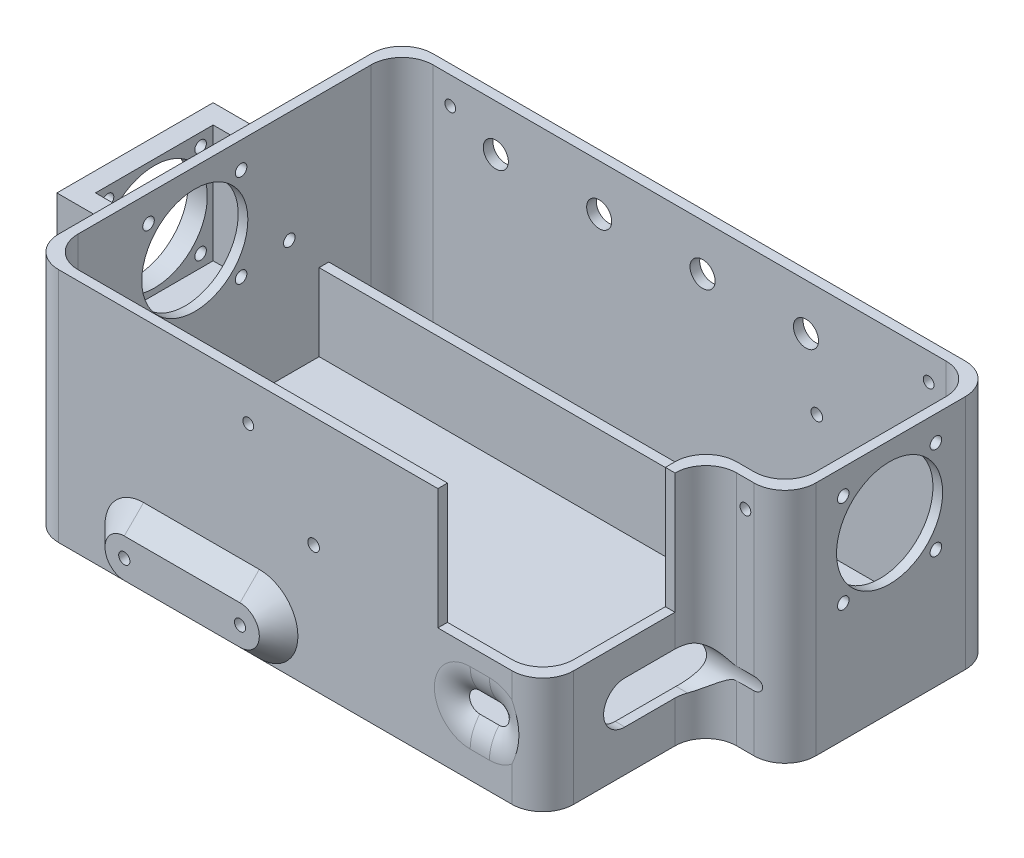
SolidWorks part; units mm, degrees
ref_plane "Front Plane" through (0, 0, 0) normal (0, 0, 1) x (1, 0, 0)
ref_plane "Top Plane" through (0, 0, 0) normal (0, 1, 0) x (1, 0, 0)
ref_plane "Right Plane" through (0, 0, 0) normal (1, 0, 0) x (0, 0, -1)
sketch "Sketch1" plane through (0, 0, 0) normal (0, 1, 0) x (1, 0, 0)
  line L1 (-74.5, 46) -> (74.5, 46)
  line L2 (-74.5, 46) -> (-74.5, -46)
  line L3 (-74.5, -46) -> (74.5, -46)
  line L4 (74.5, 46) -> (74.5, -46)
  line L5 (-74.5, 46) -> (74.5, -46) construction
  line L6 (-74.5, -46) -> (74.5, 46) construction
  point P0 (0, 0)
  dimension "D1" = 149
  dimension "D2" = 92
extrude "Boss-Extrude1" add sketch "Sketch1" along normal blind 2.5
sketch "Sketch2" plane through (0, 2.5, 0) normal (0, 1, 0) x (1, 0, 0)
  line L0 (77, -48.5) -> (77, 48.5)
  line L1 (77, 48.5) -> (-77, 48.5)
  line L2 (-77, 48.5) -> (-77, -48.5)
  line L3 (-77, -48.5) -> (77, -48.5)
  line L4 (74.5, -46) -> (74.5, 46)
  line L5 (74.5, 46) -> (-74.5, 46)
  line L6 (-74.5, 46) -> (-74.5, -46)
  line L7 (-74.5, -46) -> (74.5, -46)
  line L8 (74.5, -46) -> (74.5, 46)
  line L9 (74.5, 46) -> (-74.5, 46)
  line L10 (-74.5, 46) -> (-74.5, -46)
  line L11 (-74.5, -46) -> (74.5, -46)
  dimension "D1" = 0
  dimension "D2" = 2.5
extrude "Boss-Extrude2" add sketch "Sketch2" along normal blind 61.28 from surface at -2.5 starting at face at (0, 0, 0)
sketch "Sketch3" plane through (0, 0, 0) normal (0, 0, 1) x (1, 0, 0)
  line L0 (-77, 49.28) -> (77, 49.28) construction
  line L1 (-77, 61.28) -> (-77, 0) construction
  line L2 (77, 61.28) -> (77, 0) construction
  line L4 (-77, 61.28) -> (77, 61.28) construction
  circle A0 centre (-50.2, 49.28) radius 3.25
  circle A1 centre (-23.4, 49.28) radius 3.25
  circle A2 centre (3.4, 49.28) radius 3.25
  circle A3 centre (30.2, 49.28) radius 3.25
  dimension "D1" = 6.5
  dimension "D2" = 26.8
  dimension "D4" = 12
  dimension "D3" = 4
extrude "Cut-Extrude1" cut sketch "Sketch3" against normal blind 53.78
sketch "Sketch4" plane through (0, 2.5, 0) normal (0, 1, 0) x (1, 0, 0)
  line L0 (-74.5, -33.59) -> (74.5, -33.59) construction
  line L1 (-74.5, 46) -> (-74.5, -46) construction
  line L2 (74.5, -46) -> (74.5, 46) construction
  line L3 (-74.5, 15.41) -> (74.5, 15.41) construction
  line L4 (-74.5, 46) -> (-74.5, -46) construction
  line L5 (74.5, -46) -> (74.5, 46) construction
  line L6 (-74.5, -46) -> (74.5, -46) construction
  line L7 (-74.5, -46) -> (74.5, -46) construction
  line L8 (0, -1.375) -> (0, 1.375) construction
  line L9 (-68.5, 18.41) -> (-74.5, 18.41)
  line L10 (-68.5, 18.41) -> (-68.5, 12.41)
  line L11 (-68.5, 12.41) -> (-74.5, 12.41)
  line L12 (-74.5, 18.41) -> (-74.5, 12.41)
  line L13 (-68.5, 18.41) -> (-74.5, 12.41) construction
  line L14 (-68.5, 12.41) -> (-74.5, 18.41) construction
  line L15 (68.5, 12.41) -> (74.5, 18.41) construction
  line L16 (68.5, 18.41) -> (74.5, 12.41) construction
  line L17 (74.5, 18.41) -> (74.5, 12.41)
  line L18 (68.5, 12.41) -> (74.5, 12.41)
  line L19 (68.5, 18.41) -> (68.5, 12.41)
  line L20 (68.5, 18.41) -> (74.5, 18.41)
  line L21 (-74.5, -9.09) -> (74.5, -9.09) construction
  line L22 (-74.5, -33.59) -> (0, -9.09) construction
  line L23 (0, -9.09) -> (74.5, 15.41) construction
  line L24 (68.5, -36.59) -> (74.5, -30.59) construction
  line L25 (68.5, -30.59) -> (74.5, -36.59) construction
  line L26 (-68.5, -30.59) -> (-74.5, -36.59) construction
  line L27 (-68.5, -36.59) -> (-74.5, -30.59) construction
  line L28 (-74.5, -33.59) -> (74.5, -33.59) construction
  line L29 (68.5, -36.59) -> (74.5, -36.59)
  line L30 (68.5, -36.59) -> (68.5, -30.59)
  line L31 (68.5, -30.59) -> (74.5, -30.59)
  line L32 (74.5, -36.59) -> (74.5, -30.59)
  line L33 (-74.5, -36.59) -> (-74.5, -30.59)
  line L34 (-68.5, -30.59) -> (-74.5, -30.59)
  line L35 (-68.5, -36.59) -> (-68.5, -30.59)
  line L36 (-68.5, -36.59) -> (-74.5, -36.59)
  point P16 (-71.5, 15.41)
  point P27 (71.5, 15.41)
  point P39 (71.5, -33.59)
  point P40 (-71.5, -33.59)
  dimension "D1" = 12.41
  dimension "D2" = 61.41
  dimension "D3" = 6
  dimension "D4" = 6
sketch "Sketch5" plane through (0, 2.5, 0) normal (0, 1, 0) x (1, 0, 0)
  line L0 (-74.5, 46) -> (-74.5, -46) construction
  line L1 (-74.5, 24.5) -> (74.5, 24.5)
  line L2 (-74.5, 24.5) -> (-74.5, 27)
  line L3 (-74.5, 27) -> (74.5, 27)
  line L4 (74.5, 24.5) -> (74.5, 27)
  line L5 (74.5, -46) -> (74.5, 46) construction
  line L6 (-74.5, -46) -> (74.5, -46) construction
  dimension "D1" = 2.5
  dimension "D2" = 70.5
extrude "Boss-Extrude4" add sketch "Sketch5" along normal blind 20
sketch "Sketch6" plane through (-77, 0, 0) normal (-1, 0, 0) x (0, 0, 1)
  line L0 (-18.41, 2.5) -> (-12.41, 2.5) construction
  line L1 (48.5, 61.28) -> (48.5, 0) construction
  circle A0 centre (32.22, 32.5) radius 1.5
  circle A1 centre (-16.78, 32.5) radius 1.5
  dimension "D1" = 3
  dimension "D2" = 30
  dimension "D3" = 16.28
  dimension "D4" = 49
extrude "Cut-Extrude2" cut sketch "Sketch6" against normal up to next
sketch "Sketch8" plane through (0, 2.5, 0) normal (0, 1, 0) x (1, 0, 0)
  line L0 (-74.5, -46) -> (74.5, -46) construction
  line L1 (54, -46) -> (56.5, -46)
  line L2 (54, -46) -> (54, -6.25)
  line L3 (54, -6.25) -> (56.5, -6.25)
  line L4 (56.5, -46) -> (56.5, -6.25)
  line L5 (-74.5, 46) -> (-74.5, -46) construction
  line L6 (74.5, -46) -> (74.5, 46) construction
  line L7 (54, -6.25) -> (74.5, -6.25)
  line L8 (54, -6.25) -> (54, -3.75)
  line L9 (54, -3.75) -> (74.5, -3.75)
  line L10 (74.5, -6.25) -> (74.5, -3.75)
  line M6 (74.5, -46) -> (74.5, 24.5)
  line M9 (-74.5, -46) -> (74.5, -46)
  dimension "D1" = 2.5
  dimension "D2" = 128.5
  dimension "D3" = 39.75
  dimension "D4" = 2.5
extrude "Boss-Extrude5" add sketch "Sketch8" along normal blind 27.5 contours L4 L3 L2 M9 | L9 L8 L3 L7 M6
sketch "Sketch9" plane through (0, 61.28, 0) normal (0, 1, 0) x (1, 0, 0)
  line L1 (77, -48.5) -> (56.5, -48.5)
  line L2 (77, -48.5) -> (77, -6.25)
  line L3 (77, -6.25) -> (56.5, -6.25)
  line L4 (56.5, -48.5) -> (56.5, -6.25)
extrude "Cut-Extrude4" cut sketch "Sketch9" against normal through all
sketch "Sketch10" plane through (0, 61.28, 0) normal (0, 1, 0) x (1, 0, 0)
  line L0 (54, -3.75) -> (74.5, -3.75) construction
  line L1 (56.5, -48.5) -> (29.28, -48.5)
  line L2 (56.5, -48.5) -> (56.5, -3.75)
  line L3 (56.5, -3.75) -> (29.28, -3.75)
  line L4 (29.28, -48.5) -> (29.28, -3.75)
  dimension "D1" = 27.22
extrude "Cut-Extrude5" cut sketch "Sketch10" against normal up to surface (31.28 mm away) up to face at (61.6667, 30, 18.6667)
sketch "Sketch11" plane through (0, 22.5, 0) normal (0, 1, 0) x (1, 0, 0)
  line L0 (-74.5, 24.5) -> (74.5, 24.5) construction
  line L1 (74.5, 27) -> (34.5, 27)
  line L2 (74.5, 27) -> (74.5, 24.5)
  line L3 (74.5, 24.5) -> (34.5, 24.5)
  line L4 (34.5, 27) -> (34.5, 24.5)
  dimension "D1" = 40
extrude "Cut-Extrude6" cut sketch "Sketch11" against normal up to surface (20 mm away) up to face at (0, 2.5, -36.5)
fillet "Fillet1" radius 8 12 edges at (-74.5, 31.89, 46) (-77, 30.64, 48.5) (-74.5, 31.89, -46) (-77, 30.64, -48.5) (74.5, 31.89, -46) (77, 30.64, -48.5) (74.5, 16.25, 3.75) (77, 30.64, 6.25) (54, 16.25, 3.75) (56.5, 15, 6.25) (54, 16.25, 46) (56.5, 15, 48.5)
sketch "Sketch12" plane through (56.5, 0, 0) normal (1, 0, 0) x (0, 0, -1)
  line L0 (-56.3116, 16.25) -> (58.0085, 16.25) construction
  line L1 (24.5, 2.5) -> (-38, 2.5) construction
  line L2 (-27.25, 16.25) -> (-11.5, 16.25) construction
  line L3 (-27.25, 21.75) -> (-11.5, 21.75)
  line L4 (-27.25, 10.75) -> (-11.5, 10.75)
  line L6 (-46, 30) -> (-46, 2.5) construction
  arc A0 (-27.25, 21.75) -> (-27.25, 10.75) centre (-27.25, 16.25) ccw
  arc A1 (-11.5, 10.75) -> (-11.5, 21.75) centre (-11.5, 16.25) ccw
  point P6 (-19.375, 16.25)
  point P11 (-6, 16.25)
  point P16 (-32.75, 16.25)
  dimension "D1" = 13.75
  dimension "D2" = 40
  dimension "D3" = 11
extrude "Cut-Extrude7" cut sketch "Sketch12" against normal up to next and the other way up to next
sketch "Sketch13" plane through (0, 0, 48.5) normal (0, 0, 1) x (1, 0, 0)
  line L0 (-77, 32.5) -> (24.7107, 32.5) construction
  line L1 (-77, 0) -> (-77, 61.28) construction
  line L2 (-77, 34) -> (-77, 31) construction
  circle A0 centre (-2.92, 32.5) radius 1.5
  dimension "D2" = 3
  dimension "D1" = 74.08
extrude "Cut-Extrude8" cut sketch "Sketch13" against normal up to next
sketch "Sketch15" plane through (0, 30, 0) normal (0, 1, 0) x (1, 0, 0)
  line L0 (56.5, -14.25) -> (54, -14.25)
  line L8 (64.5, -6.25) -> (69, -6.25)
  line L9 (74.5, -4.0595) -> (74.5, 4.25)
  line L10 (66.5, -3.75) -> (62, -3.75)
  line L11 (54, -11.75) -> (54, -38)
  line L12 (46, -46) -> (29.28, -46)
  line L13 (29.28, -46) -> (29.28, -48.5)
  line L14 (29.28, -48.5) -> (48.5, -48.5)
  line L15 (56.5, -40.5) -> (56.5, -14.25)
  line L16 (64.5, -6.25) -> (69, -6.25)
  line L17 (74.5, -4.0595) -> (74.5, 4.25)
  line L18 (66.5, -3.75) -> (62, -3.75)
  line L19 (54, -11.75) -> (54, -14.25)
  arc A6 (69, -6.25) -> (74.5, -4.0595) centre (69, 1.75) ccw
  arc A7 (66.5, -3.75) -> (74.5, 4.25) centre (66.5, 4.25) ccw
  arc A8 (62, -3.75) -> (54, -11.75) centre (62, -11.75) ccw
  arc A9 (46, -46) -> (54, -38) centre (46, -38) ccw
  arc A10 (48.5, -48.5) -> (56.5, -40.5) centre (48.5, -40.5) ccw
  arc A11 (64.5, -6.25) -> (56.5, -14.25) centre (64.5, -14.25) ccw
  arc A12 (69, -6.25) -> (74.5, -4.0595) centre (69, 1.75) ccw
  arc A13 (66.5, -3.75) -> (74.5, 4.25) centre (66.5, 4.25) ccw
  arc A14 (62, -3.75) -> (54, -11.75) centre (62, -11.75) ccw
  arc A16 (48.5, -48.5) -> (56.5, -40.5) centre (48.5, -40.5) ccw
  arc A17 (64.5, -6.25) -> (56.5, -14.25) centre (64.5, -14.25) ccw
  dimension "D1" = 0
extrude "Boss-Extrude7" add sketch "Sketch15" along normal up to surface (31.28 mm away) contours L0 A10 L8 L9 L10 L11 L12 L13
sketch "Sketch17" plane through (0, 0, 48.5) normal (0, 0, 1) x (1, 0, 0)
  line L0 (37.65, 16.25) -> (42.65, 16.25) construction
  line L1 (37.65, 18.9) -> (42.65, 18.9)
  line L2 (37.65, 13.6) -> (42.65, 13.6)
  line L3 (-77, 0) -> (-77, 61.28) construction
  line L4 (-69, 0) -> (48.5, 0) construction
  arc A0 (37.65, 18.9) -> (37.65, 13.6) centre (37.65, 16.25) ccw
  arc A1 (42.65, 13.6) -> (42.65, 18.9) centre (42.65, 16.25) ccw
  point P2 (40.15, 16.25)
  dimension "D2" = 2.65
  dimension "D1" = 5
  dimension "D3" = 114.65
  dimension "D4" = 13.6
extrude "Cut-Extrude9" cut sketch "Sketch17" against normal up to next
fillet "Fillet2" radius 10 4 edges at (40.15, 18.9, 48.5) (45.3, 16.25, 48.5) (40.15, 13.6, 48.5) (35, 16.25, 48.5)
sketch "Sketch18" plane through (0, 0, -48.5) normal (0, 0, -1) x (-1, 0, 0)
  line L0 (77, 61.28) -> (77, 0) construction
  line L4 (-69, 0) -> (69, 0) construction
  circle A0 centre (-33, 32.5) radius 1.5
  dimension "D1" = 3
  dimension "D2" = 110
  dimension "D3" = 32.5
extrude "Cut-Extrude10" cut sketch "Sketch18" against normal up to next
sketch "Sketch19" plane through (-77, 0, 0) normal (-1, 0, 0) x (0, 0, 1)
  line L0 (-16.78, 32.5) -> (32.22, 32.5) construction
  line L1 (-7.53, 57.75) -> (22.97, 57.75) construction
  line L2 (-7.53, 57.75) -> (-7.53, 27.25) construction
  line L3 (-7.53, 27.25) -> (22.97, 27.25) construction
  line L4 (22.97, 57.75) -> (22.97, 27.25) construction
  line L5 (-7.53, 57.75) -> (22.97, 27.25) construction
  line L6 (-7.53, 27.25) -> (22.97, 57.75) construction
  line L7 (7.72, 32.5) -> (7.72, 92.613) construction
  line L10 (-4.28, 54.5) -> (19.72, 54.5) construction
  line L11 (-4.28, 54.5) -> (-4.28, 30.5) construction
  line L12 (-4.28, 30.5) -> (19.72, 30.5) construction
  line L13 (19.72, 54.5) -> (19.72, 30.5) construction
  line L14 (-4.28, 54.5) -> (19.72, 30.5) construction
  line L15 (-4.28, 30.5) -> (19.72, 54.5) construction
  circle A0 centre (7.72, 42.5) radius 13.75
  circle A1 centre (-4.28, 54.5) radius 1.5
  circle A2 centre (19.72, 54.5) radius 1.5
  circle A3 centre (19.72, 30.5) radius 1.5
  circle A4 centre (-4.28, 30.5) radius 1.5
  point P0 (7.72, 42.5)
  dimension "D3" = 27.5
  dimension "D6" = 3
  dimension "D1" = 30.5
  dimension "D2" = 30.5
  dimension "D4" = 10
  dimension "D5" = 24
extrude "Cut-Extrude11" cut sketch "Sketch19" against normal up to next
sketch "Sketch20" plane through (77, 0, 0) normal (1, 0, 0) x (0, 0, -1)
  line L0 (1.75, 42.5) -> (40.5, 42.5) construction
  line L1 (5.625, 58) -> (36.125, 58) construction
  line L2 (5.625, 58) -> (5.625, 27.5) construction
  line L3 (5.625, 27.5) -> (36.125, 27.5) construction
  line L4 (36.125, 58) -> (36.125, 27.5) construction
  line L5 (5.625, 58) -> (36.125, 27.5) construction
  line L6 (5.625, 27.5) -> (36.125, 58) construction
  line L7 (8.875, 54.75) -> (32.875, 54.75) construction
  line L8 (8.875, 54.75) -> (8.875, 30.75) construction
  line L9 (8.875, 30.75) -> (32.875, 30.75) construction
  line L10 (32.875, 54.75) -> (32.875, 30.75) construction
  line L11 (8.875, 54.75) -> (32.875, 30.75) construction
  line L12 (8.875, 30.75) -> (32.875, 54.75) construction
  line L13 (40.5, 0) -> (40.5, 61.28) construction
  line L14 (1.75, 61.28) -> (1.75, 0) construction
  line L15 (1.75, 0) -> (40.5, 0) construction
  circle A0 centre (20.875, 42.75) radius 13.75
  circle A1 centre (8.875, 54.75) radius 1.5
  circle A2 centre (32.875, 54.75) radius 1.5
  circle A3 centre (32.875, 30.75) radius 1.5
  circle A4 centre (8.875, 30.75) radius 1.5
  point P0 (20.875, 42.75)
  dimension "D3" = 27.5
  dimension "D6" = 3
  dimension "D1" = 30.5
  dimension "D2" = 30.5
  dimension "D4" = 42.5
  dimension "D5" = 24
extrude "Cut-Extrude12" cut sketch "Sketch20" against normal up to next
sketch "Sketch22" plane through (-77, 0, 0) normal (-1, 0, 0) x (0, 0, 1)
  line L0 (-12.53, 57.75) -> (-12.53, 22.25)
  line L1 (22.97, 57.75) -> (-7.53, 57.75) construction
  line L2 (22.97, 57.75) -> (22.97, 27.25)
  line L3 (22.97, 27.25) -> (-7.53, 27.25)
  line L4 (-7.53, 57.75) -> (-7.53, 27.25)
  line L5 (22.97, 57.75) -> (-7.53, 27.25) construction
  line L6 (22.97, 27.25) -> (-7.53, 57.75) construction
  line L7 (27.97, 22.25) -> (-12.53, 22.25)
  line L8 (27.97, 57.75) -> (27.97, 22.25)
  line L9 (27.97, 62.75) -> (-12.53, 62.75) construction
  line L10 (-7.53, 57.75) -> (-12.53, 57.75)
  line L11 (22.97, 57.75) -> (27.97, 57.75)
  line L12 (-12.53, 62.75) -> (-12.53, 57.75) construction
  line L13 (-12.53, 62.75) -> (-12.53, 22.25) construction
  line L14 (27.97, 62.75) -> (27.97, 57.75) construction
  line L15 (27.97, 62.75) -> (27.97, 22.25) construction
  point P0 (7.72, 42.5)
  dimension "D1" = 5
extrude "Boss-Extrude8" add sketch "Sketch22" along normal blind 13
sketch "Sketch23" plane through (74.5, 0, 0) normal (-1, 0, 0) x (0, 0, 1)
  line L1 (-6.125, 57.5) -> (-36.125, 57.5) construction
  line L2 (-6.125, 57.5) -> (-6.125, 27.5)
  line L3 (-6.125, 27.5) -> (-36.125, 27.5)
  line L4 (-36.125, 57.5) -> (-36.125, 27.5)
  line L5 (-6.125, 57.5) -> (-36.125, 27.5) construction
  line L6 (-6.125, 27.5) -> (-36.125, 57.5) construction
  line L7 (-41.125, 57.5) -> (-41.125, 22.5)
  line L8 (-1.125, 22.5) -> (-41.125, 22.5)
  line L9 (-1.125, 57.5) -> (-1.125, 22.5)
  line L10 (-36.125, 57.5) -> (-41.125, 57.5)
  line L11 (-6.125, 57.5) -> (-1.125, 57.5)
  line L12 (22.97, 57.75) -> (-7.53, 57.75) construction
  line L13 (-1.125, 62.5) -> (-1.125, 22.5) construction
  line L14 (-1.125, 62.5) -> (-41.125, 62.5) construction
  line L15 (-41.125, 62.5) -> (-41.125, 22.5) construction
  point P0 (-21.125, 42.5)
  dimension "D1" = 5
sketch "Sketch25" plane through (0, 0, 48.5) normal (0, 0, 1) x (1, 0, 0)
  line L0 (-69, 0) -> (48.5, 0) construction
  line L3 (-77, 0) -> (-77, 61.28) construction
  line L4 (-47, 10) -> (-17, 10) construction
  line L5 (-47, 15) -> (-17, 15)
  line L6 (-47, 5) -> (-17, 5)
  circle A2 centre (-47, 10) radius 1.45
  circle A3 centre (-17, 10) radius 1.45
  arc A4 (-47, 15) -> (-47, 5) centre (-47, 10) ccw
  arc A5 (-17, 5) -> (-17, 15) centre (-17, 10) ccw
  point P1 (-32, 10)
  dimension "D4" = 10
  dimension "D5" = 2.9
  dimension "D1" = 10
  dimension "D2" = 30
  dimension "D3" = 30
extrude "Boss-Extrude10" add sketch "Sketch25" along normal blind 5
chamfer "Chamfer4" distance 5 angle 45 4 edges at (-32, 15, 48.5) (-52, 10, 48.5) (-12, 10, 48.5) (-32, 5, 48.5)
sketch "Sketch26" plane through (0, 0, 53.5) normal (0, 0, 1) x (1, 0, 0)
  circle A0 centre (-17, 10) radius 1.45 construction
  circle A1 centre (-47, 10) radius 1.45 construction
  circle A2 centre (-17, 10) radius 1.45
  circle A3 centre (-47, 10) radius 1.45
extrude "Cut-Extrude14" cut sketch "Sketch26" against normal up to next
sketch "Sketch27" plane through (0, 0, 6.25) normal (0, 0, 1) x (1, 0, 0)
  line L0 (64.5, 61.28) -> (69, 61.28) construction
  line L1 (66.75, 61.28) -> (66.75, 50.0982) construction
  circle A0 centre (66.75, 54.28) radius 1.4
  dimension "D1" = 2.8
  dimension "D2" = 7
extrude "Cut-Extrude15" cut sketch "Sketch27" against normal blind 10
sketch "Sketch28" plane through (0, 0, -48.5) normal (0, 0, -1) x (-1, 0, 0)
  line L0 (-69, 61.28) -> (69, 61.28) construction
  line L1 (-77, 0) -> (-77, 61.28) construction
  line L2 (77, 61.28) -> (77, 0) construction
  circle A0 centre (-62, 54.28) radius 1.4
  circle A1 centre (62, 54.28) radius 1.4
  dimension "D1" = 2.8
  dimension "D2" = 7
  dimension "D3" = 15
  dimension "D4" = 15
extrude "Cut-Extrude16" cut sketch "Sketch28" against normal blind 10
sketch "Sketch29" plane through (0, 0, 48.5) normal (0, 0, 1) x (1, 0, 0)
  line L0 (-69, 61.28) -> (29.28, 61.28) construction
  line L1 (-19.86, 61.28) -> (-19.86, 43.3219) construction
  circle A0 centre (-19.86, 51.28) radius 1.4
  dimension "D2" = 2.8
  dimension "D1" = 10
extrude "Cut-Extrude17" cut sketch "Sketch29" against normal blind 10
sketch "Sketch30" plane through (-90, 0, 0) normal (-1, 0, 0) x (0, 0, 1)
  line L0 (-12.53, 57.75) -> (-12.53, 22.25) construction
  line L1 (-12.53, 57.75) -> (-12.53, 22.25)
  line L2 (27.97, 22.25) -> (27.97, 57.75) construction
  line L3 (-12.53, 22.25) -> (27.97, 22.25) construction
  line L4 (27.97, 22.25) -> (27.97, 57.75)
  line L5 (-12.53, 22.25) -> (27.97, 22.25)
  line L6 (-12.53, 57.75) -> (27.97, 57.75)
  circle A0 centre (-4.28, 30.5) radius 1.5 construction
  circle A1 centre (19.72, 30.5) radius 1.5 construction
  circle A2 centre (19.72, 54.5) radius 1.5 construction
  circle A3 centre (-4.28, 54.5) radius 1.5 construction
  circle A4 centre (7.72, 42.5) radius 13.75 construction
  circle A5 centre (-4.28, 30.5) radius 1.5
  circle A6 centre (19.72, 30.5) radius 1.5
  circle A7 centre (19.72, 54.5) radius 1.5
  circle A8 centre (-4.28, 54.5) radius 1.5
  circle A9 centre (7.72, 42.5) radius 13.75
extrude "Boss-Extrude11" add sketch "Sketch30" against normal blind 5
chamfer "Chamfer5" distance 13 angle 45 1 edges at (-77, 22.25, 7.72)
sketch "Sketch31" plane through (61.5, 0, 0) normal (-1, 0, 0) x (0, 0, 1)
  line L0 (-6.125, 57.5) -> (-6.125, 27.5) construction
  line L1 (-6.125, 27.5) -> (-36.125, 27.5) construction
  line L2 (-36.125, 27.5) -> (-36.125, 57.5) construction
  line L3 (-6.125, 57.5) -> (-6.125, 27.5)
  line L4 (-6.125, 27.5) -> (-36.125, 27.5)
  line L5 (-36.125, 27.5) -> (-36.125, 57.5)
  line L6 (-36.125, 57.5) -> (-6.125, 57.5)
  circle A0 centre (-8.875, 30.75) radius 1.5 construction
  circle A1 centre (-32.875, 30.75) radius 1.5 construction
  circle A2 centre (-20.875, 42.75) radius 13.75 construction
  circle A3 centre (-32.875, 54.75) radius 1.5 construction
  circle A4 centre (-8.875, 54.75) radius 1.5 construction
  circle A5 centre (-8.875, 30.75) radius 1.5
  circle A6 centre (-32.875, 30.75) radius 1.5
  circle A7 centre (-20.875, 42.75) radius 13.75
  circle A8 centre (-32.875, 54.75) radius 1.5
  circle A9 centre (-8.875, 54.75) radius 1.5
